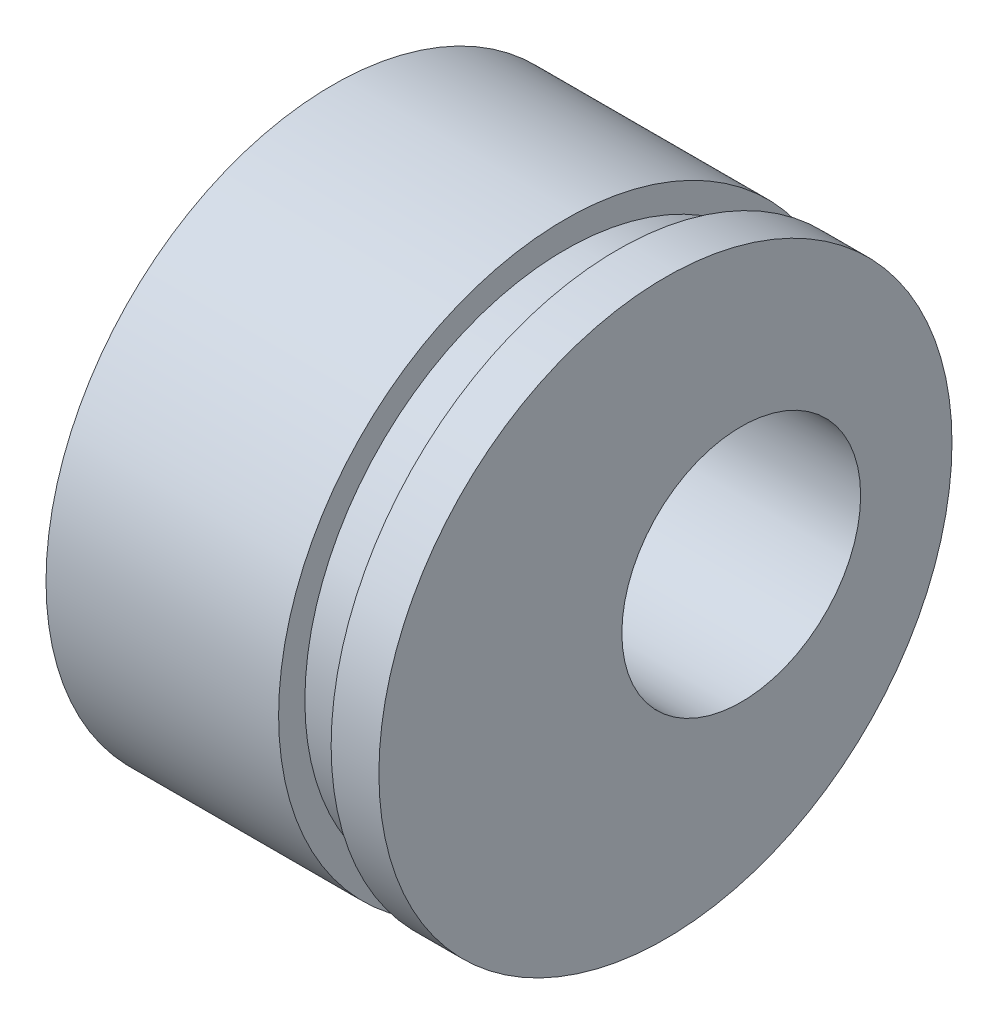
SolidWorks part; units mm, degrees
ref_plane "Front Plane" through (0, 0, 0) normal (0, 0, 1) x (1, 0, 0)
ref_plane "Top Plane" through (0, 0, 0) normal (0, 1, 0) x (1, 0, 0)
ref_plane "Right Plane" through (0, 0, 0) normal (1, 0, 0) x (0, 0, -1)
sketch "Sketch2" plane through (0, 0, 0) normal (0, 0, 1) x (1, 0, 0)
  line L0 (0, 0) -> (58.591, 0) construction
  line L2 (0, 0) -> (18.4, 0)
  line L3 (0, 0) -> (0, 2.5)
  line L4 (0, 2.5) -> (18.4, 2.5)
  line L5 (18.4, 0) -> (18.4, 2.5)
  line L6 (6, 2.5) -> (6, 6)
  line L11 (6, 6) -> (9.97, 6)
  line L16 (12.97, 6) -> (12.97, 3)
  line L17 (12.97, 3) -> (13.6304, 3)
  line L18 (13.6304, 3) -> (13.6304, 2.5)
  line L19 (13.6304, 2.5) -> (6, 2.5)
  line L22 (13.6304, 2.5) -> (16.1104, 2.5)
  line L23 (13.6304, 2.5) -> (13.6304, 4)
  line L24 (13.6304, 4) -> (16.1104, 4)
  line L25 (16.1104, 2.5) -> (16.1104, 4)
  line L27 (6, 6) -> (9.97, 6)
  line L28 (6, 6) -> (6, 9)
  line L29 (6, 9) -> (9.97, 9)
  line L30 (9.97, 6) -> (9.97, 9)
  line L31 (6, 9) -> (6, 8.25)
  line L32 (6, 8.25) -> (5, 8.25)
  line L33 (8.58, 22.001) -> (8.58, 12.476) construction
  line L34 (5, 12.476) -> (12.16, 12.476)
  line L35 (9.97, 9) -> (12.16, 9)
  line L36 (5, 7.5) -> (3, 7.5)
  line L37 (5, 8.25) -> (5, 12.476)
  line L38 (5, 7.5) -> (5, 14)
  line L39 (5, 14) -> (3, 14)
  line L40 (3, 7.5) -> (3, 14)
  line L41 (5, 22.001) -> (12.16, 22.001)
  line L42 (5, 22.001) -> (5, 30.1625)
  line L43 (5, 30.1625) -> (12.16, 30.1625)
  line L44 (12.16, 22.001) -> (12.16, 30.1625)
  line L49 (16.6304, 22.001) -> (16.6304, 7.5)
  line L51 (23.0104, 7.5) -> (23.0104, 6.5)
  line L54 (16.1104, 4) -> (13.6304, 4)
  line L56 (18.0304, 7.5) -> (23.0104, 7.5)
  line L57 (13.16, 22.001) -> (16.6304, 22.001)
  line L58 (16.1104, 3.5) -> (20.0104, 3.5)
  line L59 (29.9004, 14) -> (26.9004, 11)
  line L60 (4, 31.75) -> (18.0304, 31.75)
  line L61 (18.0304, 7.5) -> (23.0104, 7.5)
  line L62 (18.0304, 7.5) -> (18.0304, 12)
  line L63 (18.0304, 12) -> (23.0104, 12)
  line L64 (23.0104, 7.5) -> (23.0104, 12)
  line L65 (18.0304, 31.75) -> (18.0304, 12)
  line L66 (23.0104, 11) -> (26.9004, 11)
  line L67 (34.8004, 23) -> (31.3004, 19.5)
  line L68 (35.8004, 31) -> (38.7904, 33.99)
  line L69 (29.9004, 14) -> (29.9004, 15)
  line L70 (29.9004, 15) -> (22.9304, 15)
  line L71 (22.9304, 15) -> (21.0304, 15)
  line L72 (18.0304, 7.5) -> (16.6304, 7.5)
  line L73 (21.0304, 15) -> (21.0304, 43)
  line L74 (20.0304, 40) -> (10.0704, 40)
  line L75 (10.0704, 40) -> (4, 40)
  line L76 (21.0304, 43) -> (20.0304, 43)
  line L77 (22.9304, 15) -> (29.9004, 15)
  line L78 (22.9304, 15) -> (22.9304, 21)
  line L79 (22.9304, 21) -> (29.9004, 21)
  line L80 (29.9004, 15) -> (29.9004, 21)
  line L81 (10.0704, 40) -> (20.0304, 40)
  line L82 (10.0704, 40) -> (10.0704, 50)
  line L83 (10.0704, 50) -> (20.0304, 50)
  line L84 (20.0304, 40) -> (20.0304, 50)
  line L85 (4, 40) -> (4, 31.75)
  line L86 (12.97, 3) -> (12.97, 2.5)
  line L87 (31.3004, 19.5) -> (29.9004, 19.5)
  line L88 (21.51, 63.5) -> (21.51, 44)
  line L89 (21.51, 63.5) -> (25.9304, 63.5)
  line L90 (25.9304, 63.5) -> (25.9304, 25)
  line L91 (27.8304, 25) -> (25.9304, 25)
  line L92 (10.0704, 48) -> (9, 48)
  line L93 (9, 48) -> (9, 53.476)
  line L94 (9, 53.476) -> (20.0304, 53.476)
  line L95 (20.0304, 53.476) -> (20.0304, 50)
  line L96 (14.5152, 63.001) -> (14.5152, 53.476) construction
  line L97 (9, 63.001) -> (20.0304, 63.001)
  line L98 (9, 63.001) -> (9, 68.2625)
  line L99 (9, 68.2625) -> (20.0304, 68.2625)
  line L100 (20.0304, 63.001) -> (20.0304, 68.2625)
  line L101 (12.97, 6) -> (11.97, 6)
  line L102 (9, 42.5) -> (5, 42.5)
  line L103 (9, 42.5) -> (9, 55)
  line L104 (9, 55) -> (5, 55)
  line L105 (5, 42.5) -> (5, 55)
  line L106 (9.97, 6) -> (10.87, 6)
  line L107 (27.8304, 25) -> (34.8004, 25)
  line L108 (34.8004, 25) -> (34.8004, 23)
  line L109 (0, 0) -> (-2, 0)
  line L110 (0, 0) -> (0, 11)
  line L111 (27.8304, 25) -> (34.8004, 25)
  line L112 (27.8304, 25) -> (27.8304, 32.5)
  line L113 (27.8304, 32.5) -> (34.8004, 32.5)
  line L114 (34.8004, 25) -> (34.8004, 32.5)
  line L115 (35.8004, 31) -> (34.8004, 31)
  line L116 (27.8304, 32.5) -> (27.8304, 64.5)
  line L117 (21.1827, 74.025) -> (6.8477, 74.025)
  line L118 (6.8477, 74.025) -> (6.8477, 76.2)
  line L119 (38.7904, 47.29) -> (30.8304, 55.25)
  line L120 (0, 11) -> (-2, 11)
  line L121 (38.7904, 43.815) -> (30.8529, 43.815)
  line L123 (-4.8, 69.85) -> (1.55, 76.2)
  line L124 (38.7904, 47.29) -> (38.7904, 33.99)
  line L125 (-2, 0) -> (-2, 11)
  line L126 (38.7904, 37.465) -> (30.8529, 37.465)
  line L127 (30.8529, 43.815) -> (30.8529, 37.465)
  line L128 (6, 2.5) -> (6, 0)
  line L129 (0, 63.5) -> (0, 30)
  line L132 (5, 63.5) -> (0, 63.5)
  line L136 (-1.8, 30) -> (-11.76, 30)
  line L138 (-13.76, 25.4) -> (-2, 25.4)
  line L139 (-2, 25.4) -> (-2, 11.5)
  line L140 (27.8304, 64.5) -> (21.1827, 64.5)
  line L141 (-1.8, 30) -> (-11.76, 30)
  line L142 (-1.8, 30) -> (-1.8, 39)
  line L143 (-1.8, 39) -> (-11.76, 39)
  line L144 (-11.76, 30) -> (-11.76, 39)
  line L145 (21.1827, 64.5) -> (21.1827, 74.025)
  line L146 (-12.76, 37) -> (-12.76, 47.29)
  line L147 (-12.76, 37) -> (-11.76, 37)
  line L148 (30.8304, 55.25) -> (30.8304, 76.2)
  line L149 (11.97, 6) -> (11.97, 5.45)
  line L154 (-2, 11.5) -> (1, 11.5)
  line L155 (5, 60.6197) -> (24.05, 60.6197)
  line L160 (5, 60.6197) -> (5, 55.8572)
  line L161 (5, 55.8572) -> (24.05, 55.8572)
  line L166 (24.05, 60.6197) -> (24.05, 55.8572)
  line L167 (5, 60.6197) -> (24.05, 55.8572) construction
  line L172 (5, 55.8572) -> (24.05, 60.6197) construction
  line L173 (24.05, 62.2072) -> (25.9304, 62.2072)
  line L174 (11.97, 5.45) -> (10.87, 5.45)
  line L175 (10.87, 6) -> (10.87, 5.45)
  line L176 (24.05, 62.2072) -> (24.05, 54.2697)
  line L177 (24.05, 54.2697) -> (25.9304, 54.2697)
  line L178 (25.9304, 62.2072) -> (25.9304, 54.2697)
  line L179 (24.05, 62.2072) -> (25.9304, 54.2697) construction
  line L180 (24.05, 54.2697) -> (25.9304, 62.2072) construction
  line L181 (3, 19.6197) -> (15.7, 19.6197)
  line L182 (3, 19.6197) -> (3, 14.8572)
  line L183 (3, 14.8572) -> (15.7, 14.8572)
  line L184 (15.7, 19.6197) -> (15.7, 14.8572)
  line L185 (3, 19.6197) -> (15.7, 14.8572) construction
  line L186 (3, 14.8572) -> (15.7, 19.6197) construction
  line L187 (15.7, 21.2072) -> (16.6304, 21.2072)
  line L188 (15.7, 21.2072) -> (15.7, 13.2697)
  line L189 (15.7, 13.2697) -> (16.6304, 13.2697)
  line L190 (16.6304, 21.2072) -> (16.6304, 13.2697)
  line L191 (15.7, 21.2072) -> (16.6304, 13.2697) construction
  line L192 (15.7, 13.2697) -> (16.6304, 21.2072) construction
  line L193 (1, 11.5) -> (1, 6.5)
  line L194 (1, 6.5) -> (3, 6.5)
  line L195 (23.0104, 6.5) -> (20.0104, 3.5)
  line L196 (5, 63.5) -> (5, 42.5)
  line L197 (5, 42.5) -> (3, 42.5)
  line L198 (3, 42.5) -> (3, 6.5)
  line L199 (6, 0) -> (12.97, 0)
  line L200 (12.97, 0) -> (12.97, 2.5)
  line L201 (18.0304, 31.75) -> (18.0304, 35.875)
  line L202 (18.0304, 35.875) -> (21.0304, 35.875)
  line L203 (30.8304, 76.2) -> (6.8477, 76.2)
  line L204 (3.4027, 69.85) -> (7.8477, 69.85) construction
  line L205 (7.8477, 67.4687) -> (26.8977, 67.4688)
  line L206 (7.8477, 74.025) -> (7.8477, 64.5)
  line L207 (7.8477, 64.5) -> (-1.8, 64.5)
  line L208 (-1.8, 64.5) -> (-1.8, 39)
  line L209 (-12.76, 47.29) -> (-4.8, 55.25)
  line L210 (-4.8, 55.25) -> (-4.8, 69.85)
  line L211 (7.8477, 67.4687) -> (7.8477, 72.2313)
  line L212 (7.8477, 72.2313) -> (26.8977, 72.2313)
  line L213 (26.8977, 67.4688) -> (26.8977, 72.2313)
  line L214 (26.8977, 73.8187) -> (30.8304, 73.8187)
  line L215 (26.8977, 73.8187) -> (26.8977, 65.8813)
  line L216 (26.8977, 65.8813) -> (30.8304, 65.8813)
  line L217 (30.8304, 73.8187) -> (30.8304, 65.8813)
  line L218 (3.4027, 72.2313) -> (25.6277, 72.2313)
  line L219 (3.4027, 72.2313) -> (3.4027, 67.4687)
  line L220 (3.4027, 67.4687) -> (25.6277, 67.4687)
  line L221 (25.6277, 72.2313) -> (25.6277, 67.4687)
  line L222 (25.6277, 69.85) -> (21.1827, 69.85) construction
  line L223 (21.51, 44) -> (22.9304, 44)
  line L224 (22.9304, 44) -> (22.9304, 21)
  line L225 (13.6304, 4) -> (13.6304, 12.2697)
  line L226 (13.6304, 12.2697) -> (13.16, 12.2697)
  line L227 (13.16, 12.2697) -> (13.16, 22.001)
  line L228 (12.16, 9) -> (12.16, 12.476)
  line L229 (-1.8, 30) -> (0, 30)
  line L230 (9, 65.6317) -> (3.4027, 65.6317) construction
  line L231 (20.0304, 65.6317) -> (25.6277, 65.6317) construction
  line L232 (1.55, 76.2) -> (6.8477, 76.2)
  line L233 (-11.76, 30) -> (-13.76, 30)
  line L234 (-13.76, 30) -> (-13.76, 25.4)
  circle A0 centre (26.8804, 25.95) radius 0.95
  circle A1 centre (21.9804, 15.95) radius 0.95
  circle A2 centre (17.3304, 8.2) radius 0.7
  circle A3 centre (10.42, 6.45) radius 0.45
  circle A4 centre (-0.9, 30.9) radius 0.9
  point P7 (24.9902, 58.2385)
  point P131 (16.1652, 17.2385)
  point P135 (14.525, 58.2385)
  point P146 (9.35, 17.2385)
sketch "Sketch3" plane through (0, 0, 0) normal (0, 0, 1) x (1, 0, 0)
  line L0 (12.97, 3) -> (12.97, 2.5) construction
  line L1 (11.97, 6) -> (11.97, 5.45) construction
  line L2 (12.97, 6) -> (11.97, 6) construction
  line L3 (12.97, 6) -> (12.97, 3) construction
  line L5 (10.87, 6) -> (10.87, 5.45) construction
  line L6 (11.97, 5.45) -> (10.87, 5.45) construction
  line L7 (6, 2.5) -> (6, 6) construction
  line L8 (6, 6) -> (9.97, 6) construction
  line L9 (9.97, 6) -> (10.87, 6) construction
  line L10 (12.97, 3) -> (12.97, 2.5)
  line L11 (11.97, 6) -> (11.97, 5.45)
  line L12 (12.97, 6) -> (11.97, 6)
  line L13 (12.97, 6) -> (12.97, 3)
  line L15 (10.87, 6) -> (10.87, 5.45)
  line L16 (11.97, 5.45) -> (10.87, 5.45)
  line L17 (6, 2.5) -> (6, 6)
  line L18 (6, 6) -> (9.97, 6)
  line L19 (9.97, 6) -> (10.87, 6)
  line L20 (6, 2.5) -> (6, 0) construction
  line L21 (0, 0) -> (18.4, 0) construction
  line L22 (12.97, 0) -> (12.97, 2.5) construction
  line L23 (6, 2.5) -> (6, 0)
  line L24 (6, 0) -> (12.97, 0)
  line L25 (12.97, 0) -> (12.97, 2.5)
revolve "Revolve1" add sketch "Sketch3" angle 360 about L24
sketch "Sketch4" plane through (0, 0, 0) normal (1, 0, 0) x (0, 0, -1)
  line L0 (0, 0) -> (0, 69.85) construction
  line L1 (0, 0) -> (13.6271, 68.5079) construction
  line L2 (0, 0) -> (0, 58.2385) construction
  line L3 (0, 0) -> (50.436, 29.1192) construction
  line L4 (0, 0) -> (0, 31.75) construction
  line L5 (0, 0) -> (12.1502, 29.3332) construction
  line L6 (0, 0) -> (0, 17.2385) construction
  line L7 (0, 0) -> (14.929, 8.6192) construction
  line L8 (0, 0) -> (0, 58.2385) construction
  line L9 (0, 0) -> (50.436, 29.1192) construction
  line L10 (0, 0) -> (5.9583, 29.9542) construction
  line L11 (0, 0) -> (16.9677, 25.394) construction
  circle A0 centre (0, 0) radius 69.85 construction
  circle A1 centre (0, 0) radius 58.2385 construction
  circle A2 centre (0, 0) radius 31.75 construction
  circle A3 centre (0, 0) radius 17.2385 construction
  circle A4 centre (0, 69.85) radius 3.175
  circle A5 centre (0, 58.2385) radius 4.7625
  circle A6 centre (0, 31.75) radius 3.175
  circle A7 centre (0, 17.2385) radius 4.7625
  circle A8 centre (13.6271, 68.5079) radius 3.175
  circle A9 centre (26.7304, 64.533) radius 3.175
  circle A10 centre (38.8066, 58.0782) radius 3.175
  circle A11 centre (49.3914, 49.3914) radius 3.175
  circle A12 centre (58.0782, 38.8066) radius 3.175
  circle A13 centre (64.533, 26.7304) radius 3.175
  circle A14 centre (68.5079, 13.6271) radius 3.175
  circle A15 centre (69.85, 0) radius 3.175
  circle A16 centre (68.5079, -13.6271) radius 3.175
  circle A17 centre (64.533, -26.7304) radius 3.175
  circle A18 centre (58.0782, -38.8066) radius 3.175
  circle A19 centre (49.3914, -49.3914) radius 3.175
  circle A20 centre (38.8066, -58.0782) radius 3.175
  circle A21 centre (26.7304, -64.533) radius 3.175
  circle A22 centre (13.6271, -68.5079) radius 3.175
  circle A23 centre (0, -69.85) radius 3.175
  circle A24 centre (-13.6271, -68.5079) radius 3.175
  circle A25 centre (-26.7304, -64.533) radius 3.175
  circle A26 centre (-38.8066, -58.0782) radius 3.175
  circle A27 centre (-49.3914, -49.3914) radius 3.175
  circle A28 centre (-58.0782, -38.8066) radius 3.175
  circle A29 centre (-64.533, -26.7304) radius 3.175
  circle A30 centre (-68.5079, -13.6271) radius 3.175
  circle A31 centre (-69.85, 0) radius 3.175
  circle A32 centre (-68.5079, 13.6271) radius 3.175
  circle A33 centre (-64.533, 26.7304) radius 3.175
  circle A34 centre (-58.0782, 38.8066) radius 3.175
  circle A35 centre (-49.3914, 49.3914) radius 3.175
  circle A36 centre (-38.8066, 58.0782) radius 3.175
  circle A37 centre (-26.7304, 64.533) radius 3.175
  circle A38 centre (-13.6271, 68.5079) radius 3.175
  circle A47 centre (50.436, 29.1192) radius 4.7625
  circle A48 centre (50.436, -29.1192) radius 4.7625
  circle A49 centre (0, -58.2385) radius 4.7625
  circle A50 centre (-50.436, -29.1192) radius 4.7625
  circle A51 centre (-50.436, 29.1192) radius 4.7625
  circle A58 centre (12.1502, 29.3332) radius 3.175
  circle A59 centre (22.4506, 22.4506) radius 3.175
  circle A60 centre (29.3332, 12.1502) radius 3.175
  circle A61 centre (31.75, 0) radius 3.175
  circle A62 centre (29.3332, -12.1502) radius 3.175
  circle A63 centre (22.4506, -22.4506) radius 3.175
  circle A64 centre (12.1502, -29.3332) radius 3.175
  circle A65 centre (0, -31.75) radius 3.175
  circle A66 centre (-12.1502, -29.3332) radius 3.175
  circle A67 centre (-22.4506, -22.4506) radius 3.175
  circle A68 centre (-29.3332, -12.1502) radius 3.175
  circle A69 centre (-31.75, 0) radius 3.175
  circle A70 centre (-29.3332, 12.1502) radius 3.175
  circle A71 centre (-22.4506, 22.4506) radius 3.175
  circle A72 centre (14.929, 8.6192) radius 4.7625
  circle A73 centre (14.929, -8.6192) radius 4.7625
  circle A74 centre (0, -17.2385) radius 4.7625
  circle A75 centre (-14.929, -8.6192) radius 4.7625
  circle A76 centre (-14.929, 8.6192) radius 4.7625
  circle A77 centre (0, 0) radius 50
  circle A78 centre (0, 0) radius 9
  circle A79 centre (-12.1502, 29.3332) radius 3.175
  circle A80 centre (0, 0) radius 76.2
  circle A81 centre (0, 0) radius 74.025
  circle A82 centre (0, 69.85) radius 3.9687
  circle A83 centre (49.3914, 49.3914) radius 3.9687
  circle A84 centre (69.85, 0) radius 3.9688
  circle A85 centre (49.3914, -49.3914) radius 3.9687
  circle A86 centre (0, -69.85) radius 3.9687
  circle A87 centre (-49.3914, -49.3914) radius 3.9687
  circle A88 centre (-69.85, 0) radius 3.9688
  circle A89 centre (-49.3914, 49.3914) radius 3.9687
  circle A90 centre (0, 69.85) radius 2.3812
  circle A91 centre (13.6271, 68.5079) radius 2.3812
  circle A92 centre (26.7304, 64.533) radius 2.3813
  circle A93 centre (38.8066, 58.0782) radius 2.3812
  circle A94 centre (49.3914, 49.3914) radius 2.3812
  circle A95 centre (58.0782, 38.8066) radius 2.3812
  circle A96 centre (64.533, 26.7304) radius 2.3813
  circle A97 centre (68.5079, 13.6271) radius 2.3813
  circle A98 centre (69.85, 0) radius 2.3813
  circle A99 centre (68.5079, -13.6271) radius 2.3813
  circle A100 centre (64.533, -26.7304) radius 2.3813
  circle A101 centre (58.0782, -38.8066) radius 2.3812
  circle A102 centre (49.3914, -49.3914) radius 2.3812
  circle A103 centre (38.8066, -58.0782) radius 2.3812
  circle A104 centre (26.7304, -64.533) radius 2.3813
  circle A105 centre (13.6271, -68.5079) radius 2.3812
  circle A106 centre (0, -69.85) radius 2.3812
  circle A107 centre (-13.6271, -68.5079) radius 2.3812
  circle A108 centre (-26.7304, -64.533) radius 2.3813
  circle A109 centre (-38.8066, -58.0782) radius 2.3812
  circle A110 centre (-49.3914, -49.3914) radius 2.3812
  circle A111 centre (-58.0782, -38.8066) radius 2.3812
  circle A112 centre (-64.533, -26.7304) radius 2.3812
  arc A113 (3.0399, 30.8338) -> (8.9911, 29.65) centre (5.9583, 29.9542) cw
  arc A114 (14.6081, 27.3234) -> (19.6532, 23.9523) centre (16.9677, 25.394) cw
  arc A115 (23.9523, 19.6532) -> (27.3234, 14.6081) centre (25.394, 16.9677) cw
  arc A116 (29.65, 8.9911) -> (30.8338, 3.0399) centre (29.9542, 5.9583) cw
  arc A117 (30.8338, -3.0399) -> (29.65, -8.9911) centre (29.9542, -5.9583) cw
  arc A118 (27.3234, -14.6081) -> (23.9523, -19.6532) centre (25.394, -16.9677) cw
  arc A119 (19.6532, -23.9523) -> (14.6081, -27.3234) centre (16.9677, -25.394) cw
  arc A120 (8.9911, -29.65) -> (3.0399, -30.8338) centre (5.9583, -29.9542) cw
  arc A121 (-3.0399, -30.8338) -> (-8.9911, -29.65) centre (-5.9583, -29.9542) cw
  arc A122 (-14.6081, -27.3234) -> (-19.6532, -23.9523) centre (-16.9677, -25.394) cw
  arc A123 (-23.9523, -19.6532) -> (-27.3234, -14.6081) centre (-25.394, -16.9677) cw
  arc A124 (-29.65, -8.9911) -> (-30.8338, -3.0399) centre (-29.9542, -5.9583) cw
  arc A125 (-30.8338, 3.0399) -> (-29.65, 8.9911) centre (-29.9542, 5.9583) cw
  arc A126 (-27.3234, 14.6081) -> (-23.9523, 19.6532) centre (-25.394, 16.9677) cw
  arc A127 (-19.6532, 23.9523) -> (-14.6081, 27.3234) centre (-16.9677, 25.394) cw
  arc A128 (-8.9911, 29.65) -> (-3.0399, 30.8338) centre (-5.9583, 29.9542) cw
  arc A129 (26.9875, 0) -> (26.9932, 0.1932) centre (30.2705, 0) cw
  arc A130 (65.0988, 0.2771) -> (65.0875, 0) centre (68.4964, 0) ccw
  circle A131 centre (1.5875, 0) radius 40
  circle A132 centre (1.5875, 0) radius 2.5
  circle A133 centre (1.5875, 0) radius 3
  circle A134 centre (1.5875, 0) radius 43
  circle A135 centre (-68.5079, -13.6271) radius 2.3813
  circle A136 centre (-69.85, 0) radius 2.3813
  circle A137 centre (-68.5079, 13.6271) radius 2.3813
  circle A138 centre (-64.533, 26.7304) radius 2.3812
  circle A139 centre (-58.0782, 38.8066) radius 2.3812
  circle A140 centre (-49.3914, 49.3914) radius 2.3812
  circle A141 centre (-38.8066, 58.0782) radius 2.3812
  circle A142 centre (-26.7304, 64.533) radius 2.3813
  circle A143 centre (-13.6271, 68.5079) radius 2.3812
  circle A144 centre (0, 58.2385) radius 2.3812
  circle A145 centre (0, 58.2385) radius 3.9688
  circle A146 centre (50.436, 29.1192) radius 3.9688
  circle A147 centre (50.436, 29.1192) radius 2.3813
  circle A148 centre (50.436, -29.1192) radius 3.9687
  circle A149 centre (50.436, -29.1192) radius 2.3812
  circle A150 centre (0, -58.2385) radius 3.9687
  circle A151 centre (0, -58.2385) radius 2.3812
  circle A152 centre (-50.436, -29.1192) radius 3.9687
  circle A153 centre (-50.436, -29.1192) radius 2.3812
  circle A154 centre (-50.436, 29.1192) radius 3.9687
  circle A155 centre (-50.436, 29.1192) radius 2.3812
  spline S1 degree 4 poles (26.9875, 0) (26.9875, -0.0248) (26.9882, -0.0743) (26.9912, -0.1613) (26.9992, -0.2849) (27.0142, -0.4323) (27.0403, -0.5994) (27.0821, -0.7965) (27.1455, -1.0177) (27.2241, -1.2336) (27.3173, -1.4437) (27.4329, -1.6623) (27.5739, -1.8864) (27.7427, -2.1125) (27.9417, -2.3365) (28.1305, -2.5184) (28.3007, -2.6647) (28.4457, -2.7828) (28.5617, -2.8775) (28.6745, -2.9758) (28.7813, -3.0807) (28.9057, -3.2206) (29.0482, -3.4108) (29.197, -3.6576) (29.3758, -4.0447) (29.5291, -4.5502) (29.6152, -5.1612) (29.5933, -5.8758) (29.4507, -6.5869) (29.186, -7.2733) (28.8461, -7.831) (28.4818, -8.2549) (28.1375, -8.5536) (27.8792, -8.7284) (27.6484, -8.8496) (27.4154, -8.9438) (27.2144, -9.0029) (27.0118, -9.0554) (26.7709, -9.1263) (26.5334, -9.2082) (26.2634, -9.3231) (25.9685, -9.4827) (25.5538, -9.7623) (25.0678, -10.2216) (24.6281, -10.8948) (24.3613, -11.7878) (24.3459, -12.6097) (24.4764, -13.2366) (24.6525, -13.7006) (24.8058, -14.0202) (24.9382, -14.271) (25.0503, -14.5321) (25.1258, -14.8064) (25.1736, -15.0995) (25.1911, -15.4094) (25.1742, -15.8163) (25.0891, -16.3148) (24.907, -16.8764) (24.5182, -17.6315) (23.9757, -18.2942) (23.3695, -18.7764) (22.7564, -19.084) (22.3641, -19.2199) (22.0554, -19.2923) (21.7533, -19.3289) (21.4612, -19.3296) (21.1723, -19.2896) (20.8852, -19.2417) (20.5956, -19.2104) (20.3043, -19.1994) (19.8669, -19.2177) (19.2899, -19.3231) (18.5833, -19.6092) (17.8444, -20.1834) (17.3807, -20.828) (17.1316, -21.424) (17.0182, -21.8879) (16.9714, -22.1971) (16.9537, -22.4701) (16.9533, -22.7044) (16.9619, -22.9384) (16.9737, -23.1333) (16.977, -23.3286) (16.9594, -23.5624) (16.9177, -23.8101) (16.834, -24.1055) (16.6578, -24.5276) (16.3623, -25.0151) (15.9278, -25.5198) (15.3432, -25.99) (14.6957, -26.3472) (14.0068, -26.5857) (13.3856, -26.6851) (12.847, -26.6849) (12.4166, -26.6224) (12.1324, -26.5468) (11.9058, -26.4598) (11.7342, -26.3753) (11.6017, -26.2989) (11.4727, -26.2169) (11.3444, -26.1337) (11.1825, -26.0322) (10.9836, -25.9179) (10.7435, -25.7991) (10.4587, -25.6867) (10.0106, -25.5536) (9.3843, -25.468) (8.599, -25.5363) (7.7243, -25.8773) (7.1093, -26.3459) (6.716, -26.8042) (6.4745, -27.1841) (6.3352, -27.4489) (6.215, -27.7227) (6.1113, -28.0028) (5.9959, -28.2789) (5.841, -28.5357) (5.6522, -28.7792) (5.4316, -29.007) (5.1188, -29.2711) (4.6965, -29.5439) (4.1624, -29.7882) (3.5487, -29.9564) (2.9521, -30.0296) (2.386, -30.0225) (1.8595, -29.949) (1.3409, -29.8055) (0.9058, -29.6147) (0.5544, -29.4004) (0.2828, -29.1832) (0.0847, -28.9875) (-0.0865, -28.768) (-0.2353, -28.5332) (-0.3904, -28.3016) (-0.5598, -28.0786) (-0.792, -27.8146) (-1.1036, -27.5274) (-1.5105, -27.2448) (-2.0688, -26.9834) (-2.7167, -26.8202) (-3.459, -26.7949) (-4.1529, -26.9407) (-4.7224, -27.1899) (-5.1296, -27.455) (-5.3866, -27.661) (-5.5925, -27.8507) (-5.7558, -28.014) (-5.9199, -28.1766) (-6.0977, -28.3246) (-6.3382, -28.4851) (-6.6906, -28.6628) (-7.1669, -28.8182) (-7.7668, -28.9076) (-8.4201, -28.8957) (-9.0747, -28.7804) (-9.7144, -28.5614) (-10.3217, -28.2381) (-10.8061, -27.8636) (-11.1671, -27.4837) (-11.4143, -27.1402) (-11.5734, -26.859) (-11.6946, -26.573) (-11.7735, -26.2857) (-11.8173, -25.9915) (-11.8668, -25.6988) (-11.9353, -25.4093) (-12.0257, -25.1261) (-12.198, -24.7091) (-12.5089, -24.187) (-13.0379, -23.6191) (-13.8448, -23.1355) (-14.6072, -22.9365) (-15.2369, -22.9149) (-15.701, -22.9694) (-16.0024, -23.0316) (-16.2609, -23.107) (-16.4782, -23.1841) (-16.6576, -23.2529) (-16.8015, -23.307) (-16.9839, -23.3672) (-17.2087, -23.4203) (-17.4853, -23.4534) (-17.811, -23.4543) (-18.2291, -23.4104) (-18.7305, -23.2885) (-19.2884, -23.06) (-19.8603, -22.7052) (-20.3581, -22.2764) (-20.7758, -21.7899) (-21.1086, -21.2598) (-21.3336, -20.7318) (-21.4619, -20.2263) (-21.5006, -19.8113) (-21.4889, -19.4989) (-21.4468, -19.2424) (-21.3965, -19.0408) (-21.34, -18.8332) (-21.2878, -18.6168) (-21.2341, -18.3322) (-21.1962, -17.9773) (-21.1985, -17.5604) (-21.2781, -17.0173) (-21.4721, -16.4256) (-21.838, -15.7861) (-22.3482, -15.2578) (-22.8946, -14.8957) (-23.3828, -14.6878) (-23.7368, -14.5834) (-24.0536, -14.5215) (-24.3285, -14.4876) (-24.6045, -14.47) (-24.8811, -14.458) (-25.1556, -14.4184) (-25.4228, -14.3439) (-25.6932, -14.2375) (-26.1109, -14.0218) (-26.5677, -13.6822) (-27.0258, -13.1981) (-27.4314, -12.5682) (-27.7017, -11.9578) (-27.8746, -11.3112) (-27.9332, -10.727) (-27.9111, -10.2247) (-27.8415, -9.8214) (-27.7568, -9.5159) (-27.6427, -9.2298) (-27.5004, -8.9659) (-27.3212, -8.7261) (-27.1301, -8.4966) (-26.9071, -8.1967) (-26.6417, -7.7583) (-26.3997, -7.1508) (-26.2841, -6.3875) (-26.3642, -5.5798) (-26.6019, -4.9055) (-26.9193, -4.3761) (-27.2736, -3.9636) (-27.583, -3.6904) (-27.8719, -3.4871) (-28.1186, -3.3407) (-28.3135, -3.2371) (-28.5043, -3.1411) (-28.6854, -3.0419) (-28.9002, -2.8984) (-29.1355, -2.6958) (-29.4123, -2.3882) (-29.6958, -1.9552) (-29.932, -1.437) (-30.0985, -0.839) (-30.1779, -0.2025) (-30.1603, 0.4599) (-30.0348, 1.1323) (-29.8199, 1.711) (-29.5617, 2.1719) (-29.3035, 2.5118) (-29.0784, 2.748) (-28.8655, 2.924) (-28.6761, 3.0468) (-28.5112, 3.1367) (-28.3775, 3.205) (-28.2106, 3.2911) (-28.0136, 3.4005) (-27.7912, 3.5413) (-27.5508, 3.7219) (-27.2011, 4.0343) (-26.7941, 4.5285) (-26.4419, 5.234) (-26.2777, 6.1494) (-26.351, 6.9081) (-26.5268, 7.4739) (-26.7218, 7.8823) (-26.8619, 8.1196) (-26.9953, 8.3144) (-27.1373, 8.5028) (-27.2613, 8.6553) (-27.3845, 8.8088) (-27.518, 9.0035) (-27.6324, 9.2103) (-27.7412, 9.4693) (-27.8326, 9.7814) (-27.9074, 10.1885) (-27.9345, 10.6913) (-27.8808, 11.2771) (-27.6878, 12.0229) (-27.3166, 12.8111) (-26.8405, 13.4278) (-26.3243, 13.8718) (-25.9118, 14.1263) (-25.6503, 14.2566) (-25.3769, 14.3596) (-25.0933, 14.4318) (-24.8027, 14.4634) (-24.5112, 14.4738) (-24.1629, 14.5033) (-23.7608, 14.5717) (-23.1887, 14.7443) (-22.5511, 15.0901) (-21.962, 15.6231) (-21.544, 16.2749) (-21.3217, 16.857) (-21.2175, 17.3851) (-21.1902, 17.8397) (-21.2185, 18.2374) (-21.2771, 18.5739) (-21.3443, 18.8506) (-21.405, 19.0706) (-21.4579, 19.2928) (-21.4883, 19.5194) (-21.4981, 19.805) (-21.4664, 20.1907) (-21.3565, 20.6672) (-21.1331, 21.2135) (-20.8025, 21.7541) (-20.3882, 22.2461) (-19.8974, 22.677) (-19.3379, 23.033) (-18.7964, 23.2649) (-18.309, 23.3941) (-17.8981, 23.4483) (-17.5726, 23.4572) (-17.2924, 23.4331) (-17.0602, 23.3874) (-16.8337, 23.3199) (-16.6495, 23.2499) (-16.4659, 23.1791) (-16.2424, 23.1025) (-16.0156, 23.0362) (-15.7461, 22.9768) (-15.2967, 22.9185) (-14.7035, 22.9278) (-13.9592, 23.0948) (-13.1407, 23.5365) (-12.5805, 24.0908) (-12.2382, 24.6309) (-12.0505, 25.0599) (-11.9538, 25.3442) (-11.8892, 25.5989) (-11.8463, 25.8198) (-11.8162, 26.0048) (-11.7926, 26.153) (-11.7577, 26.3372) (-11.6989, 26.5548) (-11.5969, 26.8111) (-11.4414, 27.0975) (-11.1977, 27.4473) (-10.8392, 27.8343) (-10.3554, 28.2166) (-9.7549, 28.5431) (-9.1303, 28.7642) (-8.5, 28.8851) (-7.879, 28.911) (-7.3126, 28.8458) (-6.8128, 28.7091) (-6.4345, 28.54) (-6.1692, 28.378) (-5.9665, 28.2173) (-5.8163, 28.0752) (-5.6659, 27.9232) (-5.5067, 27.7699) (-5.2907, 27.5806) (-5.0072, 27.369) (-4.6509, 27.1597) (-4.148, 26.9513) (-3.5452, 26.8146) (-2.8302, 26.7991) (-2.0381, 26.9749) (-1.3495, 27.3225) (-0.8483, 27.741) (-0.5146, 28.1291) (-0.2991, 28.4338) (-0.1401, 28.6862) (0.0331, 28.93) (0.2405, 29.146) (0.4774, 29.3422) (0.7418, 29.5165) (1.1036, 29.7066) (1.5741, 29.882) (2.1471, 30.006) (2.8151, 30.041) (3.4791, 29.9721) (4.2039, 29.7804) (4.8064, 29.4933) (5.2708, 29.1628) (5.6049, 28.8311) (5.7894, 28.6062) (5.9424, 28.3744) (6.0642, 28.1249) (6.161, 27.8653) (6.2635, 27.608) (6.3813, 27.357) (6.5388, 27.0748) (6.7484, 26.7704) (7.0986, 26.3707) (7.6135, 25.9641) (8.2747, 25.644) (8.9962, 25.4959) (9.6181, 25.496) (10.1582, 25.5894) (10.5546, 25.7168) (10.8796, 25.8629) (11.1331, 26.0022) (11.3224, 26.1188) (11.5021, 26.2366) (11.6784, 26.3463) (11.9094, 26.4649) (12.2028, 26.5718) (12.6092, 26.6624) (13.1291, 26.6958) (13.7, 26.6444) (14.3062, 26.4914) (14.8974, 26.2443) (15.459, 25.9029) (15.9732, 25.4681) (16.3631, 25.0071) (16.6337, 24.567) (16.8044, 24.1822) (16.9036, 23.8716) (16.9571, 23.5978) (16.9755, 23.3672) (16.9741, 23.1748) (16.9669, 23.0211) (16.9571, 22.8289) (16.9512, 22.5982) (16.9599, 22.3287) (16.9946, 22.0224) (17.0874, 21.5638) (17.3043, 20.9714) (17.7315, 20.3087) (18.4426, 19.693) (19.1468, 19.3677) (19.739, 19.2351) (20.1882, 19.2012) (20.4852, 19.2034) (20.7812, 19.2282) (21.0745, 19.2719) (21.3675, 19.3208) (21.6648, 19.3336) (21.9737, 19.306) (22.2899, 19.241) (22.6922, 19.1116) (23.1641, 18.8854) (23.669, 18.5404) (24.1634, 18.0628) (24.569, 17.5219) (24.8807, 16.9345) (25.0937, 16.316) (25.184, 15.7743) (25.1924, 15.3317) (25.1581, 14.9969) (25.1154, 14.7695) (25.0522, 14.5468) (24.9658, 14.3321) (24.8616, 14.1257) (24.7568, 13.9198) (24.6402, 13.6649) (24.524, 13.3562) (24.3985, 12.886) (24.3389, 12.2663) (24.4166, 11.5605) (24.6979, 10.7931) (25.0952, 10.2042) (25.5426, 9.7706) (25.9551, 9.4883) (26.2689, 9.3208) (26.5627, 9.1971) (26.83, 9.1062) (27.1019, 9.0315) (27.3749, 8.9598) (27.6385, 8.8574) (27.887, 8.7225) (28.1969, 8.5098) (28.5449, 8.1936) (28.9002, 7.7549) (29.2229, 7.1817) (29.4529, 6.562) (29.5858, 5.9108) (29.6165, 5.2432) (29.5485, 4.659) (29.4188, 4.1725) (29.2636, 3.7931) (29.1144, 3.5129) (28.9404, 3.2582) (28.7432, 3.0317) (28.5155, 2.8371) (28.281, 2.6515) (28.0578, 2.4519) (27.8492, 2.2371) (27.6347, 1.9761) (27.4574, 1.7102) (27.3152, 1.4444) (27.2047, 1.1845) (27.1307, 0.9703) (27.0789, 0.7793) (27.0441, 0.6164) (27.021, 0.472) (27.0061, 0.351) (26.9981, 0.2662) (26.9946, 0.2176) (26.9932, 0.1932) knots 0.06864 0.06864 0.06864 0.06864 0.06864 0.069106 0.069571 0.070037 0.070502 0.071433 0.072364 0.073295 0.074226 0.075157 0.076088 0.077301 0.078514 0.079727 0.08094 0.081547 0.082153 0.08276 0.083366 0.083973 0.084579 0.085792 0.087214 0.088636 0.091479 0.094323 0.097166 0.100174 0.103182 0.10619 0.107694 0.109198 0.110555 0.111234 0.111912 0.113269 0.113948 0.114626 0.115983 0.11734 0.118697 0.120055 0.12408 0.128106 0.131537 0.134967 0.137266 0.138415 0.139565 0.140714 0.141863 0.143013 0.144162 0.145524 0.146885 0.149608 0.152331 0.155054 0.160594 0.163364 0.164749 0.166134 0.167314 0.168495 0.169675 0.170855 0.172035 0.173215 0.174395 0.175575 0.179125 0.182676 0.186612 0.190548 0.191813 0.193079 0.194345 0.195611 0.196244 0.196877 0.198142 0.198775 0.199408 0.200674 0.202207 0.203741 0.206808 0.209874 0.212941 0.21584 0.218738 0.221637 0.223086 0.224535 0.225775 0.226394 0.227014 0.227634 0.228253 0.228873 0.229493 0.230732 0.231971 0.233211 0.23445 0.238303 0.242155 0.245814 0.249472 0.250683 0.251894 0.253105 0.254316 0.255527 0.256738 0.257949 0.25916 0.260514 0.261868 0.264577 0.267285 0.269993 0.272142 0.27429 0.276439 0.278588 0.280839 0.281965 0.283091 0.284217 0.285343 0.286469 0.287595 0.288737 0.289879 0.292163 0.294447 0.296732 0.299827 0.302922 0.306383 0.308113 0.309844 0.31078 0.311716 0.312652 0.313588 0.314524 0.31546 0.317332 0.319969 0.322606 0.325244 0.327881 0.330703 0.333524 0.336346 0.337757 0.339168 0.340372 0.341576 0.34278 0.343984 0.345188 0.346392 0.347596 0.3488 0.352495 0.356189 0.36002 0.36385 0.365096 0.366342 0.367588 0.368834 0.369457 0.370079 0.370702 0.371325 0.372571 0.373817 0.375207 0.376596 0.379375 0.382154 0.384933 0.387459 0.389986 0.392513 0.39504 0.396723 0.398407 0.399249 0.400091 0.400932 0.401774 0.402737 0.4037 0.405625 0.407551 0.409476 0.412569 0.415662 0.41939 0.421254 0.423119 0.42424 0.425361 0.426483 0.427604 0.428726 0.429847 0.430969 0.43209 0.433431 0.437455 0.440138 0.44282 0.445528 0.448236 0.450943 0.452297 0.453651 0.454862 0.456073 0.457284 0.458495 0.459706 0.460916 0.463338 0.466783 0.470228 0.473297 0.476366 0.478273 0.480179 0.482085 0.483038 0.483991 0.484828 0.485664 0.486501 0.487337 0.48901 0.490683 0.493189 0.495695 0.498202 0.500708 0.503552 0.506397 0.509241 0.510663 0.512085 0.513303 0.514521 0.51513 0.515738 0.516347 0.516956 0.518174 0.519391 0.520609 0.521827 0.525766 0.529706 0.533208 0.53671 0.537985 0.53926 0.540535 0.541173 0.54181 0.543085 0.543723 0.54436 0.545635 0.54691 0.548267 0.549623 0.552335 0.555047 0.55776 0.562061 0.566363 0.567545 0.568728 0.56991 0.571092 0.572275 0.573457 0.574639 0.575822 0.577939 0.580057 0.584292 0.587472 0.590653 0.592493 0.594334 0.596174 0.598014 0.59894 0.599865 0.60079 0.601715 0.60264 0.603565 0.605415 0.607973 0.610531 0.61309 0.615648 0.618364 0.62108 0.623796 0.625154 0.626512 0.627788 0.629065 0.629703 0.630341 0.631618 0.632256 0.632895 0.634171 0.635448 0.636724 0.640232 0.643739 0.647674 0.651609 0.652825 0.65404 0.655256 0.656472 0.65708 0.657688 0.658296 0.658904 0.66012 0.661336 0.662756 0.664177 0.667018 0.669858 0.672699 0.675209 0.677718 0.680227 0.682736 0.684412 0.686087 0.686924 0.687762 0.688599 0.689437 0.690391 0.691345 0.693254 0.695162 0.697071 0.700143 0.703216 0.706655 0.710095 0.712514 0.713723 0.714933 0.716142 0.717352 0.718561 0.719771 0.721123 0.722475 0.725179 0.727883 0.730587 0.733273 0.735959 0.739989 0.741332 0.742455 0.743577 0.7447 0.745823 0.746945 0.748068 0.749191 0.750314 0.752181 0.754048 0.757782 0.760871 0.763961 0.765883 0.767806 0.769729 0.77069 0.771651 0.772492 0.773333 0.774174 0.775015 0.776698 0.77838 0.780903 0.783427 0.785951 0.788475 0.791257 0.794039 0.796822 0.798213 0.799604 0.800852 0.802099 0.802723 0.803347 0.803971 0.804595 0.805842 0.80709 0.808337 0.809585 0.81342 0.817255 0.820945 0.824634 0.825837 0.827039 0.828242 0.829444 0.830647 0.831849 0.833052 0.834254 0.835663 0.837072 0.83989 0.842708 0.845526 0.848167 0.850807 0.853447 0.856087 0.857024 0.857961 0.858897 0.859834 0.860771 0.861707 0.862644 0.863581 0.865314 0.867048 0.870515 0.873613 0.876711 0.880181 0.881916 0.883651 0.884794 0.885937 0.887081 0.888224 0.889367 0.89051 0.891653 0.892797 0.895451 0.898105 0.90076 0.903414 0.906126 0.908838 0.911549 0.912905 0.914261 0.915474 0.916686 0.917899 0.919111 0.920323 0.921536 0.922748 0.923961 0.925793 0.926709 0.927625 0.928541 0.929457 0.929915 0.930373 0.930831 0.931289 0.931289 0.931289 0.931289 0.931289
  spline S3 degree 4 poles (65.0875, 0) (65.0875, -0.2085) (65.1336, -0.6093) (65.3196, -1.4523) (65.739, -2.0447) (66.242, -2.6341) (66.7299, -3.0916) (67.1731, -3.6257) (67.5219, -4.2566) (67.8399, -5.1354) (68.0042, -6.2629) (67.9043, -7.3956) (67.5534, -8.464) (67.1166, -9.2437) (66.7001, -9.7852) (66.2223, -10.2316) (65.7042, -10.5824) (65.1033, -10.9671) (64.5015, -11.4984) (63.9836, -12.2541) (63.7076, -13.0981) (63.6577, -13.8665) (63.7509, -14.5541) (63.9279, -15.1344) (64.2231, -15.7099) (64.6171, -16.2749) (64.9859, -16.8848) (65.2405, -17.5795) (65.3772, -18.3315) (65.3953, -19.1188) (65.2888, -19.9454) (65.0416, -20.7887) (64.6379, -21.6235) (64.0595, -22.4019) (63.3699, -23.0372) (62.5888, -23.4701) (61.782, -23.7464) (61.0578, -24.1183) (60.3658, -24.7064) (59.8816, -25.4078) (59.6093, -26.1527) (59.5127, -26.9191) (59.5498, -27.5888) (59.7273, -28.2781) (60.0289, -28.9687) (60.2831, -29.7025) (60.3758, -30.5026) (60.3272, -31.328) (60.135, -32.1571) (59.8183, -32.9321) (59.3945, -33.6382) (58.8781, -34.2627) (58.2824, -34.7917) (57.6299, -35.2075) (56.9378, -35.4918) (56.2305, -35.6333) (55.5425, -35.7436) (54.9192, -35.9451) (54.3784, -36.2357) (53.8226, -36.6647) (53.3379, -37.2279) (52.9635, -37.9633) (52.7754, -38.8477) (52.8002, -39.6949) (52.9662, -40.4335) (53.0501, -41.0953) (53.0299, -41.6741) (52.9556, -42.1601) (52.7999, -42.7542) (52.5204, -43.4371) (52.0123, -44.2743) (51.2999, -45.0323) (50.5074, -45.5996) (49.6888, -45.9749) (49.0001, -46.1726) (48.294, -46.2386) (47.5903, -46.2021) (46.9326, -46.2102) (46.3301, -46.3235) (45.6752, -46.561) (45.0214, -46.9572) (44.4035, -47.5835) (43.9713, -48.3909) (43.7706, -49.1822) (43.7338, -49.9181) (43.7302, -50.5816) (43.6334, -51.2608) (43.4079, -51.9357) (42.9846, -52.7556) (42.2668, -53.6506) (41.3533, -54.3599) (40.3007, -54.8365) (39.3996, -55.0391) (38.7109, -55.0871) (38.0679, -55.0221) (37.4791, -54.8813) (36.7945, -54.7238) (35.9925, -54.6786) (35.0907, -54.8522) (34.2981, -55.2648) (33.7257, -55.7777) (33.3141, -56.326) (33.0345, -56.8561) (32.8392, -57.4643) (32.7053, -58.1318) (32.5057, -58.8072) (32.1692, -59.4564) (31.7161, -60.06) (31.1587, -60.6027) (30.4857, -61.0865) (29.6999, -61.483) (28.8088, -61.7584) (27.9539, -61.8544) (27.2176, -61.8147) (26.5366, -61.6724) (25.9236, -61.4387) (25.2656, -61.0978) (24.4787, -60.8476) (23.5806, -60.7805) (22.7614, -60.9343) (22.0678, -61.2531) (21.4811, -61.6931) (21.0427, -62.1588) (20.6764, -62.7331) (20.3896, -63.397) (20.0518, -64.0821) (19.5498, -64.7169) (18.9084, -65.2751) (18.1452, -65.7332) (17.3354, -66.0496) (16.5073, -66.2302) (15.682, -66.2803) (14.8803, -66.2037) (14.123, -66.0055) (13.4387, -65.6832) (12.8489, -65.2534) (12.2838, -64.832) (11.6928, -64.5309) (11.0975, -64.3539) (10.3927, -64.2676) (9.6512, -64.3301) (8.8745, -64.5906) (8.129, -65.0794) (7.5616, -65.6798) (7.1516, -66.2974) (6.7292, -66.7997) (6.2028, -67.2551) (5.5783, -67.6475) (4.7841, -67.9788) (3.8712, -68.1707) (2.9917, -68.2056) (2.1686, -68.1094) (1.418, -67.9057) (0.729, -67.5982) (0.1198, -67.1943) (-0.3827, -66.7012) (-0.8235, -66.1827) (-1.2889, -65.7455) (-1.7902, -65.4174) (-2.4157, -65.1372) (-3.1648, -64.9658) (-4.0581, -64.9888) (-4.9311, -65.2738) (-5.6111, -65.7021) (-6.1336, -66.172) (-6.5802, -66.5811) (-7.1109, -66.9505) (-7.7364, -67.2433) (-8.6229, -67.5039) (-9.7746, -67.5983) (-10.9176, -67.4218) (-11.9796, -66.988) (-12.7475, -66.4769) (-13.2722, -65.9967) (-13.6867, -65.4503) (-14.0119, -64.8723) (-14.4007, -64.2467) (-14.9594, -63.652) (-15.7285, -63.155) (-16.5724, -62.9064) (-17.3364, -62.8765) (-18.0247, -62.9861) (-18.6068, -63.179) (-19.1862, -63.4909) (-19.784, -63.8646) (-20.4334, -64.1501) (-21.1317, -64.3118) (-22.0298, -64.3813) (-22.9982, -64.2701) (-23.9891, -63.9533) (-24.8397, -63.4681) (-25.4154, -63.007) (-25.8399, -62.5635) (-26.1408, -62.1749) (-26.4394, -61.6789) (-26.6877, -61.0599) (-26.9007, -60.3339) (-27.2894, -59.581) (-27.8821, -58.8987) (-28.6764, -58.362) (-29.5588, -58.0865) (-30.4418, -58.0554) (-31.2145, -58.2063) (-31.8698, -58.4438) (-32.557, -58.6637) (-33.3003, -58.7515) (-34.0729, -58.7048) (-34.8508, -58.5315) (-35.6055, -58.2363) (-36.3189, -57.8248) (-36.9719, -57.301) (-37.5423, -56.6697) (-37.9855, -55.9721) (-38.293, -55.2278) (-38.4273, -54.4632) (-38.4985, -53.7131) (-38.6773, -53.0244) (-38.9694, -52.4208) (-39.4251, -51.7974) (-40.0241, -51.2777) (-40.7875, -50.8987) (-41.6779, -50.7194) (-42.492, -50.745) (-43.3317, -50.8952) (-44.2251, -50.8964) (-45.1368, -50.6758) (-46.0207, -50.2762) (-46.7791, -49.7422) (-47.4046, -49.125) (-47.899, -48.4541) (-48.2653, -47.7574) (-48.5109, -47.0338) (-48.6258, -46.3032) (-48.5997, -45.5912) (-48.5294, -44.9062) (-48.55, -44.26) (-48.6763, -43.6668) (-48.9279, -43.0203) (-49.3438, -42.3723) (-49.994, -41.7677) (-50.8134, -41.3575) (-51.5975, -41.1841) (-52.3098, -41.1392) (-52.9334, -41.0842) (-53.5681, -40.9261) (-54.1954, -40.6549) (-54.9562, -40.1853) (-55.7818, -39.4216) (-56.4191, -38.48) (-56.8229, -37.4145) (-56.9716, -36.4922) (-56.973, -35.7718) (-56.8456, -35.0891) (-56.6436, -34.4482) (-56.4711, -33.7221) (-56.4502, -32.8948) (-56.649, -32.0092) (-57.1254, -31.1487) (-57.7708, -30.51) (-58.4838, -30.0886) (-59.1915, -29.8498) (-59.8427, -29.6823) (-60.4903, -29.4299) (-61.1017, -29.048) (-61.8067, -28.434) (-62.498, -27.5279) (-62.9605, -26.4892) (-63.1725, -25.385) (-63.1692, -24.4916) (-63.0682, -23.8162) (-62.8676, -23.1941) (-62.5852, -22.636) (-62.2465, -22.0084) (-61.9776, -21.2523) (-61.8906, -20.3405) (-62.058, -19.4685) (-62.3866, -18.772) (-62.8014, -18.2154) (-63.2376, -17.7934) (-63.775, -17.4329) (-64.3938, -17.1299) (-65.0127, -16.7759) (-65.5728, -16.2922) (-66.0577, -15.701) (-66.4559, -15.0213) (-66.7642, -14.2468) (-66.9575, -13.3897) (-67.0099, -12.464) (-66.8823, -11.503) (-66.5881, -10.6131) (-66.1159, -9.8554) (-65.5448, -9.2225) (-65.0917, -8.5465) (-64.7714, -7.6968) (-64.6877, -6.8487) (-64.8104, -6.065) (-65.0973, -5.3476) (-65.4544, -4.7796) (-65.9438, -4.2625) (-66.5428, -3.8049) (-67.1216, -3.2868) (-67.5915, -2.6323) (-67.9498, -1.8869) (-68.1844, -1.0686) (-68.2839, -0.2372) (-68.2562, 0.5859) (-68.1079, 1.3824) (-67.8442, 2.1339) (-67.4759, 2.814) (-67.0091, 3.3986) (-66.4598, 3.8656) (-65.9118, 4.2957) (-65.4645, 4.7738) (-65.1323, 5.2899) (-64.854, 5.9343) (-64.7029, 6.6617) (-64.7315, 7.4865) (-64.9956, 8.3514) (-65.4279, 9.0808) (-65.9316, 9.6463) (-66.3266, 10.1843) (-66.5902, 10.7002) (-66.7614, 11.1612) (-66.9138, 11.7564) (-67.0011, 12.4893) (-66.9634, 13.468) (-66.7086, 14.4765) (-66.2914, 15.3572) (-65.7582, 16.0825) (-65.2524, 16.5896) (-64.6675, 16.9902) (-64.0348, 17.2999) (-63.4636, 17.6256) (-62.9917, 18.0165) (-62.5341, 18.5414) (-62.154, 19.2046) (-61.9168, 20.0519) (-61.9299, 20.9678) (-62.1378, 21.7576) (-62.4626, 22.4193) (-62.7816, 23.0012) (-63.0271, 23.6422) (-63.1578, 24.3419) (-63.186, 25.2645) (-62.9931, 26.3956) (-62.5388, 27.4592) (-61.8502, 28.3868) (-61.1611, 29.0013) (-60.5826, 29.3776) (-59.9893, 29.6331) (-59.4065, 29.7959) (-58.7317, 29.9901) (-58.0084, 30.339) (-57.3037, 30.9276) (-56.8101, 31.6725) (-56.5578, 32.3986) (-56.4634, 33.0779) (-56.4757, 33.6773) (-56.5996, 34.3042) (-56.8066, 34.953) (-56.9602, 35.6406) (-56.9815, 36.3717) (-56.8785, 37.1197) (-56.6546, 37.865) (-56.3011, 38.615) (-55.8067, 39.3425) (-55.1614, 40.0175) (-54.361, 40.5839) (-53.4966, 40.9773) (-52.6075, 41.1366) (-51.7446, 41.1582) (-50.9354, 41.3217) (-50.1173, 41.6976) (-49.4752, 42.2292) (-49.0228, 42.8441) (-48.7227, 43.5135) (-48.5648, 44.1335) (-48.5227, 44.8135) (-48.594, 45.5334) (-48.6316, 46.2966) (-48.501, 47.0955) (-48.2113, 47.8952) (-47.7665, 48.6665) (-47.2121, 49.3364) (-46.5757, 49.8963) (-45.8787, 50.3408) (-45.1409, 50.663) (-44.3829, 50.8574) (-43.6284, 50.9082) (-42.9043, 50.8189) (-42.206, 50.7245) (-41.5433, 50.7476) (-40.937, 50.8811) (-40.2788, 51.1471) (-39.7262, 51.5171) (-39.2658, 51.9893) (-38.9131, 52.5364) (-38.7001, 53.0023) (-38.5499, 53.5113) (-38.4639, 54.0546) (-38.4035, 54.6217) (-38.285, 55.1987) (-38.0677, 55.7784) (-37.7559, 56.3461) (-37.3536, 56.8882) (-36.8608, 57.3907) (-36.292, 57.8353) (-35.653, 58.2093) (-34.9511, 58.4983) (-34.1963, 58.6846) (-33.445, 58.7504) (-32.7165, 58.6934) (-32.0379, 58.5065) (-31.4011, 58.2671) (-30.7824, 58.1104) (-30.1851, 58.0663) (-29.5022, 58.1242) (-28.8849, 58.3025) (-28.3189, 58.5985) (-27.8275, 58.9947) (-27.4878, 59.3597) (-27.1867, 59.7905) (-26.9404, 60.2842) (-26.7513, 60.8312) (-26.5595, 61.406) (-26.2751, 61.9869) (-25.8703, 62.5469) (-25.2217, 63.2054) (-24.2606, 63.8474) (-23.1756, 64.248) (-22.0367, 64.3843) (-21.1176, 64.3105) (-20.426, 64.1457) (-19.7984, 63.8696) (-19.2337, 63.5223) (-18.5906, 63.1637) (-17.814, 62.9143) (-16.9006, 62.8522) (-16.0419, 63.0435) (-15.3589, 63.3875) (-14.8097, 63.817) (-14.3938, 64.268) (-14.0381, 64.8219) (-13.6968, 65.439) (-13.2677, 66.0042) (-12.7357, 66.4849) (-11.9841, 66.982) (-11.0834, 67.3551) (-10.0633, 67.5591) (-9.0842, 67.548) (-8.3573, 67.4245) (-7.771, 67.243) (-7.3194, 67.0495) (-6.8176, 66.7612) (-6.3001, 66.3409) (-5.7617, 65.8096) (-5.0573, 65.3395) (-4.2083, 65.0299) (-3.2534, 64.9451) (-2.3479, 65.1316) (-1.5602, 65.5324) (-0.9572, 66.039) (-0.4992, 66.5647) (-0.0052, 67.091) (0.6022, 67.5289) (1.3004, 67.8634) (2.0648, 68.0897) (2.8681, 68.1981) (3.6915, 68.1846) (4.5166, 68.0438) (5.3215, 67.769) (6.0475, 67.3745) (6.6776, 66.8734) (7.1664, 66.2705) (7.5924, 65.6494) (8.0825, 65.1337) (8.6303, 64.7473) (9.3308, 64.4229) (10.1065, 64.2585) (10.958, 64.2968) (11.8239, 64.5715) (12.5238, 64.9885) (13.1854, 65.5275) (13.9659, 65.9629) (14.8703, 66.2129) (15.8374, 66.2928) (16.7598, 66.1942) (17.6064, 65.9582) (18.3641, 65.6118) (19.0225, 65.1808) (19.5884, 64.6677) (20.0436, 64.0851) (20.3665, 63.4503) (20.6373, 62.8174) (20.9684, 62.2624) (21.3662, 61.8048) (21.8993, 61.3614) (22.5769, 60.996) (23.4387, 60.7819) (24.3544, 60.8201) (25.1246, 61.0485) (25.7695, 61.3547) (26.3415, 61.6097) (26.9734, 61.7799) (27.6537, 61.8476) (28.5471, 61.8066) (29.6399, 61.5397) (30.6542, 61.0259) (31.5244, 60.2907) (32.1021, 59.5569) (32.4531, 58.9281) (32.6734, 58.2697) (32.8078, 57.6116) (33.0089, 56.8932) (33.3912, 56.1596) (33.9941, 55.4813) (34.8277, 54.9592) (35.7018, 54.7131) (36.53, 54.6899) (37.2651, 54.8241) (37.916, 54.9939) (38.6049, 55.0879) (39.3251, 55.0511) (40.2399, 54.8566) (41.2843, 54.4001) (42.1929, 53.7166) (42.9143, 52.8543) (43.3452, 52.0721) (43.5848, 51.4329) (43.7116, 50.792) (43.7359, 50.1672) (43.7441, 49.4543) (43.8752, 48.663) (44.2408, 47.8232) (44.8096, 47.1415) (45.4346, 46.6913) (46.0673, 46.4052) (46.6536, 46.2474) (47.2985, 46.1925) (47.9868, 46.2278) (48.7, 46.219) (49.4249, 46.0682) (50.1361, 45.7868) (50.8145, 45.3859) (51.4601, 44.8584) (52.0452, 44.2029) (52.5404, 43.4193) (52.8953, 42.5175) (53.0703, 41.597) (53.0258, 40.7056) (52.8338, 39.8754) (52.765, 39.0648) (52.8965, 38.1665) (53.2341, 37.384) (53.7212, 36.7578) (54.3199, 36.2691) (54.9077, 35.9453) (55.5867, 35.7301) (56.3327, 35.6205) (57.0905, 35.4488) (57.8193, 35.1048) (58.4947, 34.6271) (59.0973, 34.0254) (59.5881, 33.3468) (59.9634, 32.6138) (60.2205, 31.8456) (60.3547, 31.0608) (60.363, 30.2877) (60.2391, 29.5502) (59.9859, 28.8754) (59.7153, 28.2337) (59.5559, 27.5989) (59.5154, 26.9867) (59.5841, 26.2884) (59.8043, 25.5789) (60.2289, 24.8712) (60.8791, 24.2424) (61.611, 23.8136) (62.326, 23.5634) (62.9328, 23.285) (63.4141, 22.962) (63.7877, 22.642) (64.2101, 22.1956) (64.6425, 21.5971) (65.0848, 20.7231) (65.3517, 19.7177) (65.4145, 18.7455) (65.3007, 17.8528) (65.1049, 17.1641) (64.7884, 16.53) (64.3858, 15.9523) (64.0442, 15.3907) (63.8209, 14.8203) (63.675, 14.1396) (63.6638, 13.3754) (63.8667, 12.5192) (64.3219, 11.7243) (64.8867, 11.1339) (65.4917, 10.7124) (66.0534, 10.3584) (66.5796, 9.9173) (67.0339, 9.369) (67.5068, 8.5758) (67.8873, 7.4932) (68.0066, 6.3429) (67.855, 5.1978) (67.5512, 4.3262) (67.2284, 3.7166) (66.8341, 3.2056) (66.4039, 2.7793) (65.9959, 2.3684) (65.6608, 1.9383) (65.4055, 1.4839) (65.2226, 0.982) (65.1371, 0.5988) (65.1074, 0.3834) (65.0988, 0.2771) knots 0.070151 0.070151 0.070151 0.070151 0.070151 0.071893 0.073635 0.074839 0.076042 0.077245 0.078449 0.079818 0.081187 0.083925 0.086561 0.087879 0.089198 0.090319 0.091441 0.092563 0.093684 0.095431 0.097177 0.099043 0.099975 0.100908 0.102141 0.103374 0.104607 0.105841 0.107249 0.108657 0.110066 0.111474 0.113209 0.114943 0.116677 0.118412 0.119867 0.121323 0.122778 0.124234 0.12632 0.127363 0.128406 0.129755 0.131103 0.132451 0.1338 0.13532 0.136841 0.138361 0.139881 0.141306 0.142731 0.144156 0.14558 0.146828 0.148076 0.149324 0.150572 0.151515 0.152459 0.154345 0.155857 0.157368 0.15888 0.160391 0.161271 0.162151 0.163031 0.163911 0.16567 0.16743 0.170022 0.171318 0.172613 0.173875 0.175136 0.176397 0.177658 0.178588 0.179518 0.181379 0.183098 0.184818 0.186006 0.187193 0.188381 0.189569 0.190921 0.192274 0.194979 0.197739 0.199119 0.200498 0.201583 0.202668 0.203753 0.204837 0.20662 0.208402 0.210245 0.211167 0.212088 0.213307 0.214526 0.215744 0.216963 0.218354 0.219746 0.221137 0.222528 0.224283 0.226038 0.227793 0.22867 0.229548 0.231022 0.232497 0.233971 0.235446 0.23742 0.238408 0.239395 0.240689 0.241984 0.243279 0.244573 0.246164 0.247754 0.249345 0.250935 0.252375 0.253816 0.255256 0.256696 0.257959 0.259221 0.260484 0.261746 0.2627 0.263654 0.265562 0.267037 0.268512 0.269987 0.271463 0.27234 0.273218 0.274973 0.276729 0.278484 0.279875 0.281266 0.282657 0.284048 0.285266 0.286484 0.287703 0.288921 0.289842 0.290763 0.292606 0.294388 0.296171 0.297257 0.298342 0.299427 0.300512 0.301893 0.303273 0.306034 0.308738 0.31009 0.311442 0.312629 0.313816 0.315004 0.316191 0.31791 0.319629 0.32149 0.32242 0.323351 0.324612 0.325874 0.327136 0.328398 0.329694 0.33099 0.333582 0.335342 0.337101 0.33798 0.33886 0.339739 0.340619 0.34213 0.343641 0.345152 0.346663 0.34855 0.350437 0.351686 0.352934 0.354182 0.355431 0.356856 0.358281 0.359706 0.361131 0.362651 0.364171 0.365691 0.367211 0.368559 0.369907 0.371255 0.372603 0.373646 0.374689 0.376774 0.37823 0.379686 0.381142 0.382599 0.384333 0.386068 0.387803 0.389538 0.390946 0.392354 0.393762 0.39517 0.396403 0.397636 0.398868 0.400101 0.401034 0.401966 0.40383 0.405578 0.407325 0.408447 0.409569 0.410691 0.411813 0.413132 0.41445 0.417088 0.419825 0.421194 0.422562 0.423765 0.424968 0.426171 0.427374 0.429115 0.430857 0.4326 0.434342 0.435546 0.43675 0.437954 0.439158 0.440527 0.441897 0.444636 0.447271 0.448589 0.449907 0.451028 0.452149 0.45327 0.454391 0.456137 0.457883 0.459749 0.460682 0.461615 0.462849 0.464082 0.465316 0.46655 0.467959 0.469367 0.470776 0.472185 0.473919 0.475653 0.477386 0.47912 0.480575 0.48203 0.483485 0.48494 0.487027 0.48807 0.489114 0.490463 0.491811 0.49316 0.494509 0.49603 0.497551 0.499071 0.500592 0.502016 0.503441 0.504865 0.506289 0.507537 0.508784 0.510032 0.511279 0.512222 0.513165 0.515052 0.516564 0.518076 0.519588 0.5211 0.52198 0.52286 0.52374 0.52462 0.526381 0.528141 0.530732 0.532027 0.533322 0.534583 0.535844 0.537105 0.538366 0.539295 0.540225 0.542085 0.543805 0.545525 0.546713 0.547902 0.54909 0.550278 0.551631 0.552984 0.55569 0.558449 0.559828 0.561207 0.562292 0.563376 0.56446 0.565544 0.567326 0.569108 0.570952 0.571873 0.572795 0.574014 0.575234 0.576453 0.577672 0.579064 0.580456 0.581848 0.583239 0.584994 0.586748 0.588502 0.590256 0.59173 0.593204 0.594678 0.596152 0.598127 0.599115 0.600102 0.601397 0.602692 0.603987 0.605282 0.606873 0.608464 0.610055 0.611646 0.613086 0.614526 0.615966 0.617405 0.618668 0.61993 0.621192 0.622454 0.623408 0.624361 0.626268 0.627184 0.6281 0.629016 0.629932 0.630989 0.632045 0.633102 0.634159 0.635418 0.636677 0.637936 0.639195 0.640586 0.641976 0.643367 0.644757 0.645975 0.647193 0.648411 0.649629 0.65055 0.65147 0.653312 0.654204 0.655095 0.655987 0.656879 0.657964 0.65905 0.660136 0.661221 0.662602 0.663983 0.666745 0.669448 0.6708 0.672151 0.673338 0.674525 0.675712 0.676899 0.678617 0.680336 0.682197 0.683128 0.684059 0.685321 0.686583 0.687845 0.689107 0.690404 0.6917 0.694294 0.696052 0.697811 0.69869 0.699569 0.700449 0.701328 0.702838 0.704349 0.705859 0.707369 0.709257 0.711145 0.712394 0.713643 0.714891 0.71614 0.717566 0.718991 0.720417 0.721843 0.723362 0.724882 0.726401 0.72792 0.729268 0.730616 0.731964 0.733311 0.734354 0.735396 0.737481 0.738938 0.740394 0.741851 0.743308 0.745043 0.746779 0.748514 0.75025 0.751657 0.753065 0.754472 0.755879 0.757112 0.758344 0.759577 0.760809 0.761741 0.762673 0.764537 0.766285 0.768032 0.769155 0.770277 0.7714 0.772522 0.773842 0.775161 0.777799 0.780535 0.781904 0.783272 0.784474 0.785677 0.786879 0.788081 0.789822 0.791563 0.793307 0.79505 0.796254 0.797459 0.798663 0.799867 0.801237 0.802607 0.805347 0.807982 0.809299 0.810616 0.811737 0.812858 0.813978 0.815099 0.816845 0.81859 0.820456 0.82139 0.822323 0.823557 0.824791 0.826025 0.827259 0.828668 0.830078 0.831487 0.832896 0.83463 0.836363 0.838096 0.839829 0.841284 0.842738 0.844193 0.845647 0.847735 0.848778 0.849822 0.851171 0.85252 0.853869 0.855219 0.85674 0.858261 0.859782 0.861304 0.862727 0.864151 0.865575 0.866999 0.868246 0.869493 0.87074 0.871987 0.87293 0.873873 0.875758 0.877271 0.878784 0.880296 0.881809 0.882689 0.88357 0.88445 0.885331 0.887092 0.888852 0.891442 0.892737 0.894032 0.895292 0.896553 0.897813 0.899073 0.900003 0.900932 0.902791 0.904512 0.906233 0.907422 0.90861 0.909799 0.910987 0.912341 0.913694 0.916401 0.919159 0.920538 0.921917 0.923 0.924084 0.925168 0.926252 0.927142 0.928033 0.928924 0.929815 0.929815 0.929815 0.929815 0.929815
  point P116 (0, 0)
  point P225 (0, 0)
sketch "Sketch5" plane through (0, 0, 0) normal (1, 0, 0) x (0, 0, -1)
  circle A0 centre (1.5875, 0) radius 2.5 construction
  circle A1 centre (1.5875, 0) radius 2.5
extrude "Cut-Extrude1" cut sketch "Sketch5" along normal through all
